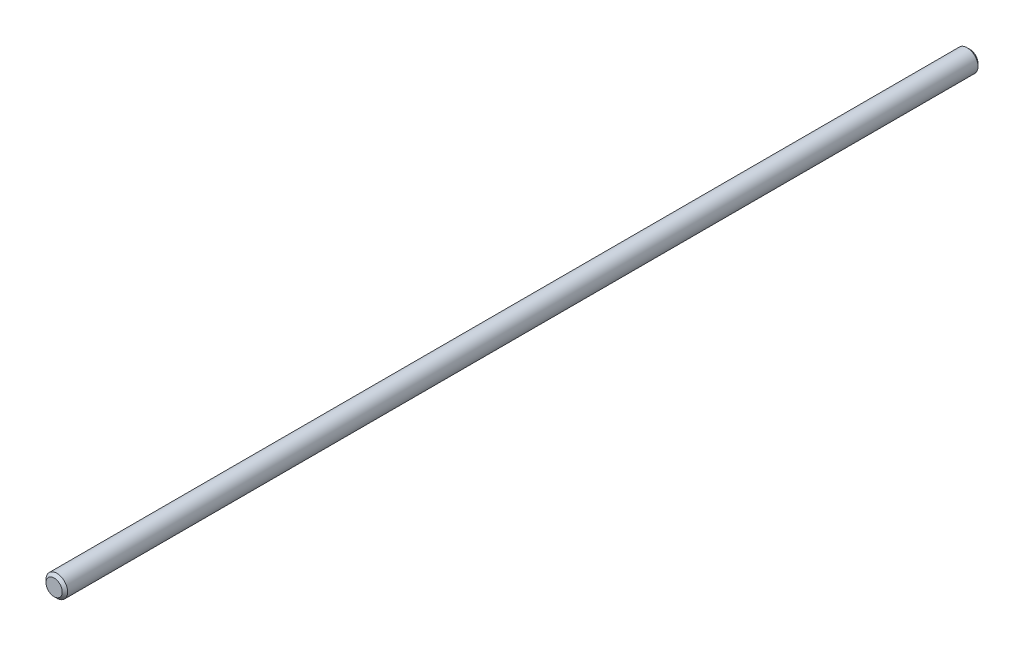
SolidWorks part; units mm, degrees
ref_plane "Piano frontale" through (0, 0, 0) normal (0, 0, 1) x (1, 0, 0)
ref_plane "Piano superiore" through (0, 0, 0) normal (0, 1, 0) x (1, 0, 0)
ref_plane "Piano destro" through (0, 0, 0) normal (1, 0, 0) x (0, 0, -1)
sketch "Schizzo1" plane through (0, 0, 0) normal (0, 0, 1) x (1, 0, 0)
  circle A0 centre (0, 0) radius 4
  dimension "D1" = 8
extrude "Estrusione-Estrusione1" add sketch "Schizzo1" along normal blind 338
chamfer "Smusso1" distance 1 angle 45 2 edges at (4, 0, 338) (4, 0, 0)
sketch "Schizzo2" plane through (0, 0, 0) normal (0, 1, 0) x (1, 0, 0)
  line L0 (4, -337) -> (4, -1) construction
  line L1 (4, -337) -> (4, -1) construction
  line L2 (4, -337) -> (-4, -337) construction
  line L3 (4, -1) -> (-4, -1) construction
